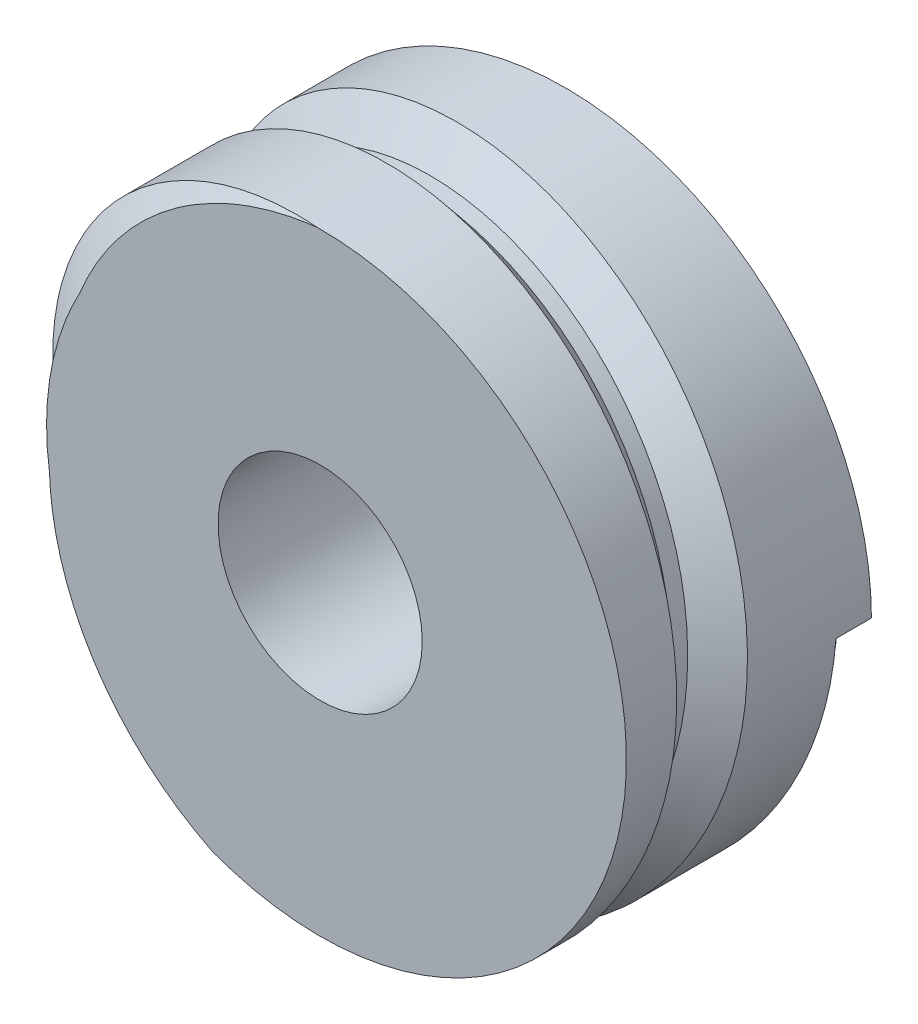
SolidWorks part; units mm, degrees
ref_plane "Front Plane" through (0, 0, 0) normal (0, 0, 1) x (1, 0, 0)
ref_plane "Top Plane" through (0, 0, 0) normal (0, 1, 0) x (1, 0, 0)
ref_plane "Right Plane" through (0, 0, 0) normal (1, 0, 0) x (0, 0, -1)
sketch "Sketch1" plane through (0, 0, 0) normal (0, 0, 1) x (1, 0, 0)
  circle A0 centre (0, 0) radius 9.525
  dimension "D1" = 19.05
extrude "Boss-Extrude1" add sketch "Sketch1" along normal blind 7.62 contours A0
sketch "Sketch2" plane through (0, 0, 7.62) normal (0, 0, 1) x (1, 0, 0)
  circle A0 centre (0, 0) radius 3.175
  dimension "D1" = 6.35
extrude "Cut-Extrude1" cut sketch "Sketch2" against normal through all
sketch "Sketch3" plane through (0, 0, 0) normal (0, 0, -1) x (-1, 0, 0)
  circle A0 centre (0, 0) radius 9.525 construction
  circle A1 centre (0, 0) radius 9.525
curve "Helix/Spiral1" pitch 4.986 height 7.62 turns 1.5283
sketch "Sketch5" plane through (0, 0, 7.62) normal (0, 0, 1) x (1, 0, 0)
  line L0 (9.3789, -1.6619) -> (-9.3789, 1.6619) construction
  circle A0 centre (0, 0) radius 9.525 construction
  point P6 (0, 0)
ref_plane "Plane2" through (0, 0, 0) normal (0.1745, 0.9847, 0) x (-0.9847, 0.1745, 0)
sketch "Sketch6" plane through (0, 0, 0) normal (0.1745, 0.9847, 0) x (-0.9847, 0.1745, 0)
  line L0 (10.033, 6.096) -> (10.033, 9.144)
  line L1 (10.033, 9.144) -> (8.509, 7.874)
  line L2 (8.509, 7.366) -> (10.033, 6.096)
  line L3 (-9.525, 7.62) -> (9.525, 7.62) construction
  line L4 (8.509, 7.62) -> (10.033, 7.62) construction
  line L5 (8.509, 7.874) -> (8.509, 7.366)
  line L6 (10.033, 7.62) -> (8.509, 7.62) construction
  line L7 (8.255, 7.62) -> (-9.525, 7.62) construction
  line L10 (9.525, 7.62) -> (-9.525, 7.62) construction
  line L11 (9.525, 7.62) -> (8.509, 7.62) construction
  point P2 (10.033, 7.62)
  point P17 (8.509, 7.62)
  dimension "D1" = 1.27
  dimension "D2" = 0.508
  dimension "D3" = 3.048
  dimension "D4" = 0.254
  dimension "D5" = 0.508
sweep "Cut-Sweep5" cut profiles "Sketch6" path "Helix/Spiral1"
